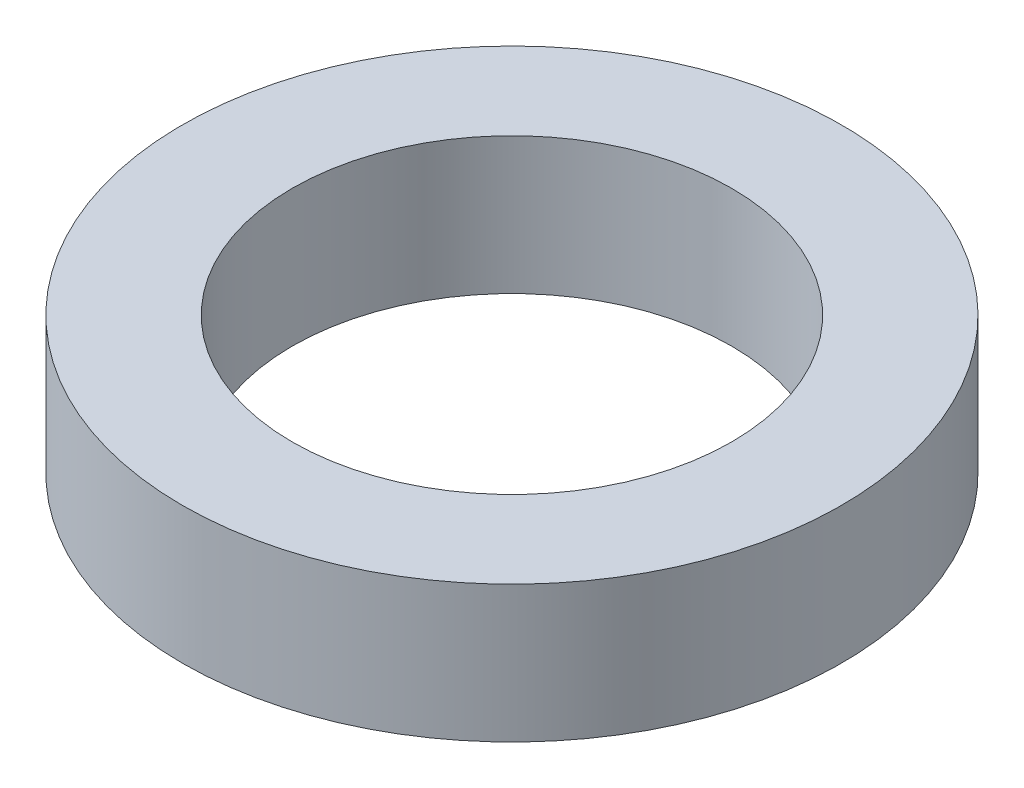
SolidWorks part; units mm, degrees
ref_plane "Front Plane" through (0, 0, 0) normal (0, 0, 1) x (1, 0, 0)
ref_plane "Top Plane" through (0, 0, 0) normal (0, 1, 0) x (1, 0, 0)
ref_plane "Right Plane" through (0, 0, 0) normal (1, 0, 0) x (0, 0, -1)
sketch "Sketch1" plane through (0, 0, 0) normal (0, 1, 0) x (1, 0, 0)
  circle A0 centre (0, 0) radius 67.5
  dimension "FLANGE_OD" = 135
extrude "Boss-Extrude1" add sketch "Sketch1" along normal blind 28
sketch "Sketch2" plane through (0, 0, 0) normal (0, 1, 0) x (1, 0, 0)
  circle A0 centre (0, 0) radius 45
  dimension "BORE_D" = 90
extrude "Cut-Extrude1" cut sketch "Sketch2" along normal through all
sketch "Sketch3" plane through (0, 28, 0) normal (0, 1, 0) x (1, 0, 0)
  circle A0 centre (0, 0) radius 26.6566 construction
  circle A1 centre (-26.6566, 0) radius 3.2359
  dimension "BOLT_D" = 6.4717
  dimension "BOLT_PCD" = 53.3132
extrude "Cut-Extrude2" cut sketch "Sketch3" against normal blind 22.7462 rebuild error yes
pattern_circular "CirPattern1" count 8 over 360 rebuild error yes
